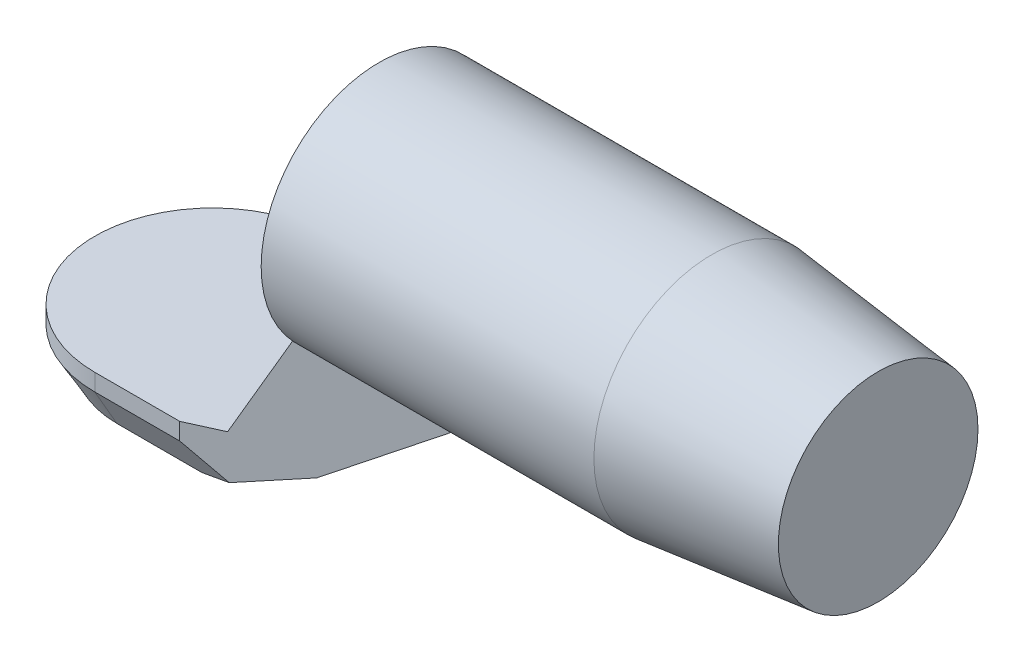
SolidWorks part; units mm, degrees
material "6061 Alloy"
ref_plane "Front Plane" through (0, 0, 0) normal (0, 0, 1) x (1, 0, 0)
ref_plane "Top Plane" through (0, 0, 0) normal (0, 1, 0) x (1, 0, 0)
ref_plane "Right Plane" through (0, 0, 0) normal (1, 0, 0) x (0, 0, -1)
sketch "Sketch1" plane through (0, 0, 0) normal (1, 0, 0) x (0, 0, -1)
  circle A0 centre (0, 0) radius 22.86
  dimension "D1" = 45.72
ref_plane "Plane1" through (-38.1, 0, 0) normal (1, 0, 0) x (0, 0, -1)
sketch "Sketch2" plane through (-38.1, 0, 0) normal (1, 0, 0) x (0, 0, -1)
  circle A0 centre (0, 0) radius 27
  dimension "D1" = 54
loft "Loft1" add profiles "Sketch2", "Sketch1" connector at (-38.1, 5.3922, -26.4561) connector at (0, 4.7494, -22.3612)
sketch "Sketch5" plane through (0, 0, 0) normal (0, 0, 1) x (1, 0, 0)
  line L0 (0, 0) -> (-215.6011, 0) construction
  line L1 (-73.7601, 19.0263) -> (-121.9075, 52.7) construction
  line L2 (-132.9431, -52.7) -> (-111.3493, -45.3158)
  line L3 (-121.9075, 52.7) -> (-179.4, 52.7) construction
  line L4 (-179.4, 52.7) -> (-179.4, 40) construction
  line L5 (-179.4, 40) -> (-125.4, 40) construction
  line L6 (-125.4, 40) -> (-101.1914, -9.1173) construction
  line L7 (-101.1914, -9.1173) -> (-73.7601, 19.0263) construction
  line L8 (-152.4, 40) -> (-152.4, 0) construction
  line L9 (-132.9431, 52.7) -> (-111.3493, 45.3158) construction
  line L10 (-101.1914, 9.1173) -> (-73.7601, -19.0263)
  line L11 (-125.4, -40) -> (-101.1914, 9.1173)
  line L12 (-179.4, -40) -> (-125.4, -40)
  line L13 (-179.4, -52.7) -> (-179.4, -40)
  line L14 (-121.9075, -52.7) -> (-179.4, -52.7)
  line L15 (-73.7601, -19.0263) -> (-121.9075, -52.7)
  dimension "D1" = 40
  dimension "D2" = 152.4
  dimension "D3" = 54
  dimension "D4" = 12.7
extrude "Boss-Extrude3" add sketch "Sketch5" along normal blind 27 and the other way blind 27 contours L9 L3 L4 L5 L6 L7 L1 | L15 L10 L11 L12 L13 L14 L2 region at (-118.6956, -29.9426, 0)
sketch "Sketch6" plane through (0, -40, 0) normal (0, 1, 0) x (1, 0, 0)
  line L0 (-86.2505, 5.8489) -> (-132.9431, 27)
  line L1 (-132.9431, -27) -> (-86.2505, -5.8489)
  line L2 (-132.9431, -27) -> (-96.6058, -77.5731)
  line L3 (-96.6058, -77.5731) -> (-73.5917, -70.7461)
  line L4 (-73.5917, -70.7461) -> (-57.2697, 82.0167)
  line L5 (-57.2697, 82.0167) -> (-91.2428, 97.7499)
  line L6 (-91.2428, 97.7499) -> (-132.9431, 27)
  line L7 (0, -22.86) -> (0, 22.86) construction
  line L8 (-179.4, 27) -> (-125.4, 27) construction
  line L9 (-179.4, -27) -> (-125.4, -27) construction
  line L10 (-88.9, 0) -> (-73.7601, 0) construction
  line L13 (-73.7601, 27) -> (-73.7601, -27) construction
  arc A0 (-86.2505, -5.8489) -> (-86.2505, 5.8489) centre (-88.9, 0) ccw
  dimension "D1" = 88.9
extrude "Cut-Extrude1" cut sketch "Sketch6" along normal through all and the other way through all
sketch "Sketch3" plane through (-38.1, 0, 0) normal (-1, 0, 0) x (0, 0, 1)
  circle A0 centre (0, 0) radius 27 construction
  circle A1 centre (0, 0) radius 27
extrude "Boss-Extrude1" add sketch "Sketch3" along normal blind 76.2
ref_axis "Spherical Roll" through (-274.9024, 0, 0) along (1, 0, 0)
sketch "Sketch4" plane through (0, 0, 0) normal (0, 1, 0) x (1, 0, 0)
  line L1 (-38.1, -28.477) -> (-38.1, 28.477) construction
  circle A0 centre (-114.3, 0) radius 25.4
  dimension "D1" = 50.8
  dimension "D2" = 76.2
ref_point "Pt"
ref_axis "Axis4" through (-114.3, -29.7, 0) along (0, 1, 0)
ref_axis "Axis5" through (-114.3, 0, 29.7) along (0, 0, -1)
sketch "Sketch7" plane through (0, -40, 0) normal (0, 1, 0) x (1, 0, 0)
  line L1 (-152.4, 27) -> (-158.7502, 40.6901)
  line L2 (-158.7502, 40.6901) -> (-204.2521, 19.5838)
  line L3 (-204.2521, 19.5838) -> (-213.553, -44.4785)
  line L4 (-213.553, -44.4785) -> (-177.8, -47.5336)
  line L5 (-177.8, -47.5336) -> (-152.4, -27)
  circle A0 centre (-152.4, 0) radius 27
  dimension "D1" = 54
extrude "Cut-Extrude5" cut sketch "Sketch7" against normal through all contours L4 L5 L1 L2 L3 | A0 | A0 region at (-186.9765, -40, 9.7469)
chamfer "Chamfer1" distance 5.08 angle 60 3 edges at (-142.6716, -52.7, -27) (-142.6716, -52.7, 27) (-179.4, -52.7, 0) first distance on face at (-149.4216, -52.7, 0)
